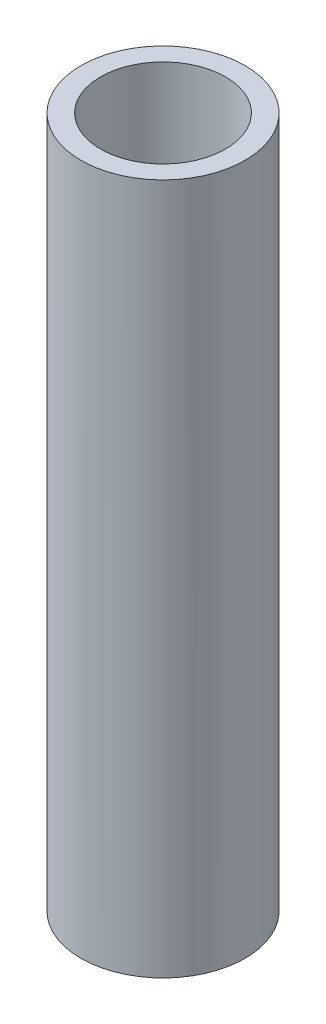
SolidWorks part; units mm, degrees
material "AISI 316 Stainless Steel Sheet (SS)"
ref_plane "Front Plane" through (0, 0, 0) normal (0, 0, 1) x (1, 0, 0)
ref_plane "Top Plane" through (0, 0, 0) normal (0, 1, 0) x (1, 0, 0)
ref_plane "Right Plane" through (0, 0, 0) normal (1, 0, 0) x (0, 0, -1)
sketch "Sketch1" plane through (0, 0, 0) normal (0, 1, 0) x (1, 0, 0)
  circle A0 centre (0, 0) radius 1.05
  circle A1 centre (0, 0) radius 0.8
  dimension "D1" = 2.1
  dimension "D2" = 1.6
extrude "Boss-Extrude1" add sketch "Sketch1" along normal offset from surface (8.841 mm away) 4 contours A1 | A0 offset beyond the face yes
